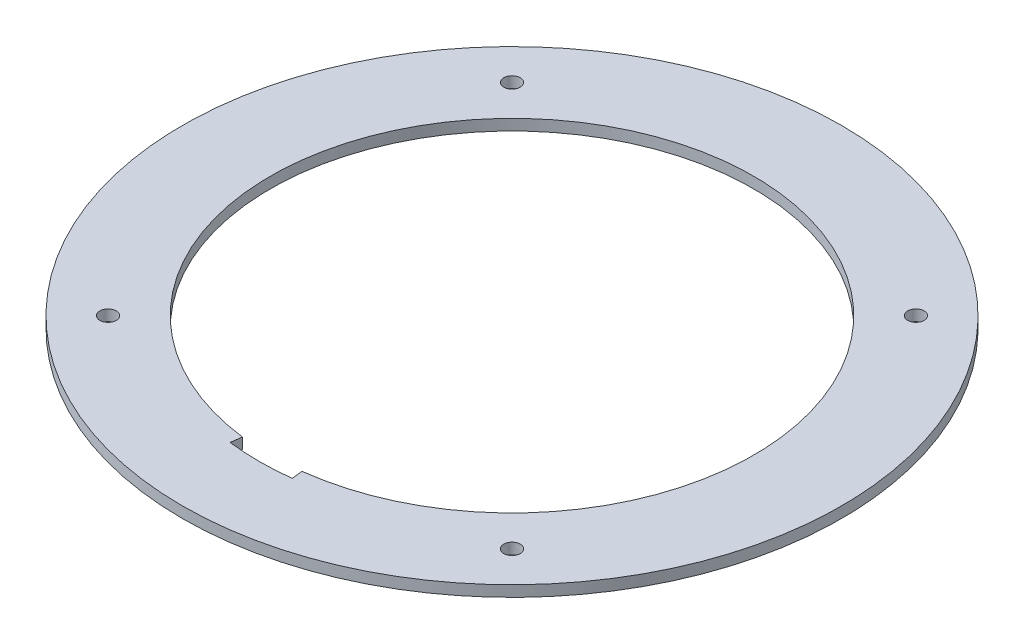
SolidWorks part; units mm, degrees
note: The reader was unsure of these and kept them because the rebuilt part matched: thickness of "基体-法兰1", "钣金6", "钣金7".
ref_plane "前视基准面" through (0, 0, 0) normal (0, 0, 1) x (1, 0, 0)
ref_plane "上视基准面" through (0, 0, 0) normal (0, 1, 0) x (1, 0, 0)
ref_plane "右视基准面" through (0, 0, 0) normal (1, 0, 0) x (0, 0, -1)
sketch "草图1" plane through (0, 0, 0) normal (0, 1, 0) x (1, 0, 0)
  line L0 (-5.6627, -45.6501) -> (-5.4165, -43.6653)
  line L1 (5.6634, -45.65) -> (5.4171, -43.6653)
  arc A0 (5.4171, -43.6653) -> (-5.4165, -43.6653) centre (0, 0) ccw
  circle A1 centre (0, 0) radius 60
  arc A2 (5.6634, -45.65) -> (-5.6627, -45.6501) centre (0, 0) cw
  dimension "D1" = 88
  dimension "D2" = 120
  dimension "D3" = 46
base flange "基体-法兰1" sketch "草图1" thickness 2 reverse thickness direction no parameters "D1"=0.7366
sketch "草图6" plane through (0, 0, 0) normal (0, 1, 0) x (1, 0, 0)
  line L0 (0, 60) -> (0, -60) construction
  line L1 (-60, 0) -> (60, 0) construction
  line L2 (-36.7696, 36.7696) -> (36.7696, -36.7696) construction
  circle A0 centre (36.7696, 36.7696) radius 1.5
  circle A4 centre (0, 0) radius 60 construction
  circle A5 centre (-36.7696, 36.7696) radius 1.5
  circle A6 centre (36.7696, -36.7696) radius 1.5
  circle A7 centre (-36.7696, -36.7696) radius 1.5
  dimension "D1" = 3
  dimension "D3" = 3
  dimension "D4" = 52
extrude "切除-拉伸1" cut sketch "草图6" against normal up to next normal cut yes
sketch "折弯-线1" plane through (0, 0, 0) normal (0, 1, 0) x (1, 0, 0)
sketch "边界框1" plane through (0, 0, 0) normal (0, 1, 0) x (1, 0, 0)
sheet metal parameters "钣金6" thickness 2 parameters "D1"=0.7366
flat pattern "平板型式6" [suppressed]
sketch "折弯-线2" plane through (0, 0, 0) normal (0, 1, 0) x (1, 0, 0)
sketch "边界框2" [suppressed] plane through (0, 0, 0) normal (0, 1, 0) x (1, 0, 0)
sheet metal parameters "钣金7" thickness 2 parameters "D1"=0.7366, "D7"=3
flat pattern "平板型式6"
sketch "折弯-线2" plane through (0, 0, 0) normal (0, 1, 0) x (1, 0, 0)
sketch "边界框2" [suppressed] plane through (0, 0, 0) normal (0, 1, 0) x (1, 0, 0)
